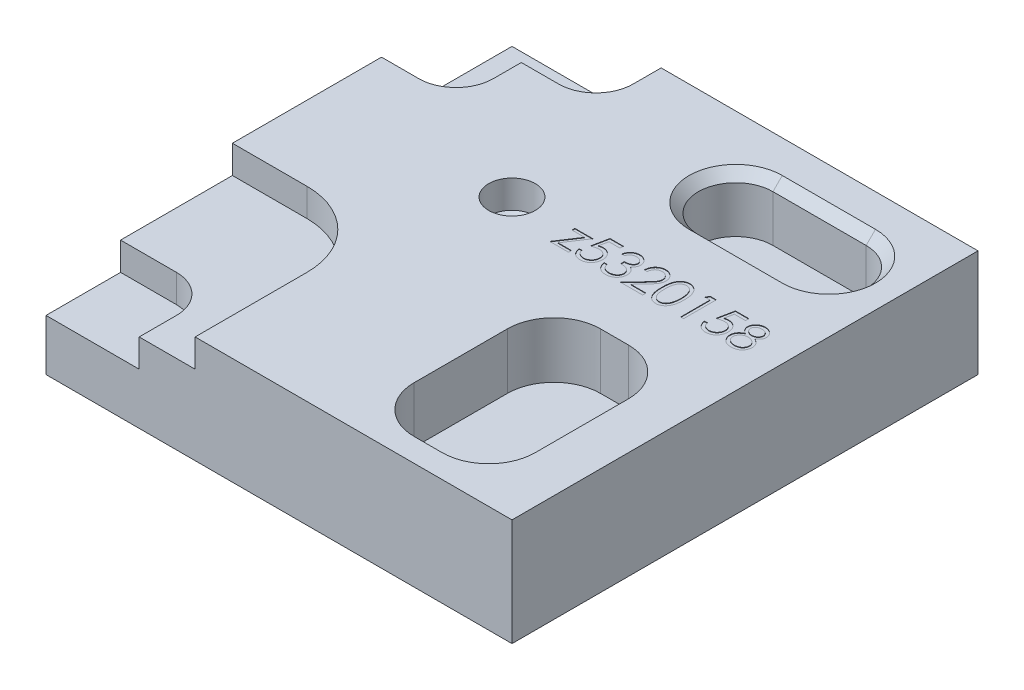
SolidWorks part; units mm, degrees
material "Alumina"
ref_plane "Front Plane" through (0, 0, 0) normal (0, 0, 1) x (1, 0, 0)
ref_plane "Top Plane" through (0, 0, 0) normal (0, 1, 0) x (1, 0, 0)
ref_plane "Right Plane" through (0, 0, 0) normal (1, 0, 0) x (0, 0, -1)
sketch "Sketch1" plane through (0, 0, 0) normal (0, 1, 0) x (1, 0, 0)
  line L0 (-4.643, 19.7567) -> (-4.643, 16.7567)
  line L1 (-20.643, 19.7567) -> (29.357, 19.7567)
  line L2 (-20.643, 19.7567) -> (-20.643, -30.2433)
  line L3 (-20.643, -30.2433) -> (29.357, -30.2433)
  line L4 (29.357, 19.7567) -> (29.357, -30.2433)
  line L5 (-20.643, 5.7567) -> (-16.643, 5.7567)
  line L6 (-12.643, 12.7567) -> (-12.643, 9.7567)
  line L7 (-12.643, 9.7567) -> (-12.643, 12.7567)
  line L8 (-8.643, 12.7567) -> (-12.643, 12.7567)
  line L9 (11.857, 7.2567) -> (21.857, 7.2567)
  line L15 (11.857, 15.2567) -> (21.857, 15.2567)
  line L17 (-20.643, -10.2433) -> (-12.643, -10.2433)
  line L18 (16.357, -5.2433) -> (19.357, -5.2433)
  line L19 (11.357, -10.2433) -> (11.357, -22.7433)
  line L20 (16.357, -27.7433) -> (19.357, -27.7433)
  line L21 (24.357, -10.2433) -> (24.357, -22.7433)
  line L22 (-4.643, -18.2433) -> (-4.643, -30.2433)
  line L23 (-20.643, -22.2433) -> (-14.643, -22.2433)
  line L24 (-10.643, -26.2433) -> (-10.643, -30.2433)
  arc A0 (-16.643, 5.7567) -> (-12.643, 9.7567) centre (-16.643, 9.7567) ccw
  arc A1 (-8.643, 12.7567) -> (-4.643, 16.7567) centre (-8.643, 16.7567) ccw
  arc A2 (21.857, 15.2567) -> (21.857, 7.2567) centre (21.857, 11.2567) cw
  arc A3 (11.857, 15.2567) -> (11.857, 7.2567) centre (11.857, 11.2567) ccw
  arc A4 (16.357, -5.2433) -> (11.357, -10.2433) centre (16.357, -10.2433) ccw
  arc A5 (24.357, -10.2433) -> (19.357, -5.2433) centre (19.357, -10.2433) ccw
  arc A6 (19.357, -27.7433) -> (24.357, -22.7433) centre (19.357, -22.7433) ccw
  arc A7 (11.357, -22.7433) -> (16.357, -27.7433) centre (16.357, -22.7433) ccw
  arc A8 (-10.643, -26.2433) -> (-14.643, -22.2433) centre (-14.643, -26.2433) ccw
  arc A9 (-4.643, -18.2433) -> (-12.643, -10.2433) centre (-12.643, -18.2433) ccw
  circle A10 centre (-0.643, -0.2433) radius 1.5
  circle A11 centre (-0.643, -0.2433) radius 2.5
  point P41 (-16.643, -10.2433)
  dimension "D7" = 4
  dimension "D8" = 4
  dimension "D11" = 4.5
  dimension "D13" = 5
  dimension "D14" = 5
  dimension "D15" = 5
  dimension "D16" = 5
  dimension "D21" = 4
  dimension "D22" = 8
  dimension "D27" = 3
  dimension "D28" = 5
  dimension "D1" = 50
  dimension "D2" = 50
  dimension "D3" = 14
  dimension "D4" = 16
  dimension "D5" = 8
  dimension "D6" = 7
  dimension "D9" = 10
  dimension "D10" = 8
  dimension "D12" = 7.5
  dimension "D17" = 22.5
  dimension "D18" = 18
  dimension "D19" = 5
  dimension "D20" = 2.5
  dimension "D23" = 10
  dimension "D24" = 20
  dimension "D25" = 8
  dimension "D26" = 16
  dimension "D29" = 30
  dimension "D30" = 20
extrude "Boss-Extrude1" add sketch "Sketch1" along normal blind 11.5 contours L3 L4 L1 L2
sketch "Sketch3" plane through (0, 11.5, 0) normal (0, 1, 0) x (1, 0, 0)
  line L0 (-20.643, -10.2433) -> (-12.643, -10.2433)
  line L1 (-20.643, 19.7567) -> (-20.643, -30.2433) construction
  line L2 (-4.643, -18.2433) -> (-4.643, -30.2433)
  line L3 (-20.643, -30.2433) -> (29.357, -30.2433) construction
  line L8 (-20.643, 19.7567) -> (-20.643, -30.2433)
  line L9 (-20.643, -30.2433) -> (29.357, -30.2433)
  line L10 (29.357, -30.2433) -> (29.357, 19.7567)
  line L11 (29.357, 19.7567) -> (-20.643, 19.7567)
  line L12 (-20.643, -10.2433) -> (-20.643, -30.2433)
  line L13 (-20.643, -30.2433) -> (-4.643, -30.2433)
  arc A0 (-4.643, -18.2433) -> (-12.643, -10.2433) centre (-12.643, -18.2433) ccw
  dimension "D1" = 8
  dimension "D2" = 20
  dimension "D3" = 16
  dimension "D4" = 0
extrude "Cut-Extrude1" cut sketch "Sketch3" against normal blind 3 contours L0 A0 L2 L13 L12
sketch "Sketch7" plane through (0, 8.5, 0) normal (0, 1, 0) x (1, 0, 0)
  line L0 (-20.643, -22.2433) -> (-14.643, -22.2433)
  line L1 (-20.643, -10.2433) -> (-20.643, -30.2433) construction
  line L2 (-10.643, -26.2433) -> (-10.643, -30.2433)
  line L3 (-20.643, -30.2433) -> (-4.643, -30.2433) construction
  arc A0 (-10.643, -26.2433) -> (-14.643, -22.2433) centre (-14.643, -26.2433) ccw
  dimension "D1" = 4
  dimension "D2" = 8
  dimension "D3" = 10
extrude "Cut-Extrude4" cut sketch "Sketch7" against normal blind 3 and the other way through all flip side to cut
sketch "Sketch8" plane through (0, 11.5, 0) normal (0, 1, 0) x (1, 0, 0)
  line L0 (-4.643, -30.2433) -> (29.357, -30.2433) construction
  line L1 (16.357, -7.7433) -> (19.357, -7.7433)
  line L2 (11.357, -12.7433) -> (11.357, -22.7433)
  line L3 (16.357, -27.7433) -> (19.357, -27.7433)
  line L4 (24.357, -12.7433) -> (24.357, -22.7433)
  line L5 (29.357, 19.7567) -> (29.357, -30.2433) construction
  arc A0 (16.357, -27.7433) -> (11.357, -22.7433) centre (16.357, -22.7433) cw
  arc A1 (19.357, -27.7433) -> (24.357, -22.7433) centre (19.357, -22.7433) ccw
  arc A2 (24.357, -12.7433) -> (19.357, -7.7433) centre (19.357, -12.7433) ccw
  arc A3 (16.357, -7.7433) -> (11.357, -12.7433) centre (16.357, -12.7433) ccw
  dimension "D1" = 5
  dimension "D2" = 22.5
  dimension "D3" = 2.5
  dimension "D4" = 5
  dimension "D5" = 18
extrude "Cut-Extrude5" cut sketch "Sketch8" against normal blind 6
sketch "Sketch9" plane through (0, 11.5, 0) normal (0, 1, 0) x (1, 0, 0)
  line L0 (-4.643, -30.2433) -> (29.357, -30.2433) construction
  line L1 (-20.643, 19.7567) -> (-20.643, -10.2433) construction
  circle A0 centre (-0.643, -0.2433) radius 1.5
  dimension "D1" = 3
  dimension "D2" = 30
  dimension "D3" = 20
sketch "Sketch11" plane through (0, 11.5, 0) normal (0, 1, 0) x (1, 0, 0)
  line L0 (29.357, 19.7567) -> (29.357, -30.2433) construction
  line L1 (11.857, 15.2567) -> (21.857, 15.2567)
  line L3 (11.857, 7.2567) -> (21.857, 7.2567)
  line L7 (-20.643, 19.7567) -> (29.357, 19.7567) construction
  arc A0 (21.857, 15.2567) -> (21.857, 7.2567) centre (21.857, 11.2567) cw
  arc A1 (11.857, 15.2567) -> (11.857, 7.2567) centre (11.857, 11.2567) ccw
  dimension "D1" = 10
  dimension "D3" = 8
  dimension "D2" = 7.5
  dimension "D4" = 4.5
extrude "Cut-Extrude8" cut sketch "Sketch11" against normal blind 6
sketch "Sketch12" plane through (0, 11.5, 0) normal (0, 1, 0) x (1, 0, 0)
  line L0 (-20.643, 5.7567) -> (-16.643, 5.7567)
  line L1 (-20.643, 19.7567) -> (-20.643, -10.2433) construction
  line L2 (-4.643, 19.7567) -> (-4.643, 16.7567)
  line L4 (-8.643, 12.7567) -> (-12.643, 12.7567)
  line L5 (-12.643, 12.7567) -> (-12.643, 9.7567)
  line L6 (-20.643, 19.7567) -> (29.357, 19.7567) construction
  arc A0 (-12.643, 9.7567) -> (-16.643, 5.7567) centre (-16.643, 9.7567) cw
  arc A1 (-8.643, 12.7567) -> (-4.643, 16.7567) centre (-8.643, 16.7567) ccw
  point P16 (-12.643, 11.2567)
  dimension "D1" = 4
  dimension "D2" = 4
  dimension "D3" = 14
  dimension "D4" = 16
  dimension "D5" = 8
  dimension "D6" = 7
extrude "Cut-Extrude11" cut sketch "Sketch12" against normal blind 6 and the other way through all flip side to cut contours L2 A1 L4 L5 A0 L0
chamfer "Chamfer1" distance 1 angle 45 4 edges at (7.857, 11.5, -11.2567) (16.857, 11.5, -7.2567) (25.857, 11.5, -11.2567) (16.857, 11.5, -15.2567)
hole_wizard "Ø3.0mm Dowel Hole1" positions "3DSketch3" profile "Sketch15" hole size "Ø3.0" standard "ANSI Metric"
sketch3d "3DSketch3"
  point P0 (-0.643, 11.5, 0.2433)
sketch "Sketch15" plane through (-0.643, 11.5, 0.2433) normal (1, 0, 0) x (0, 0, 1)
  line L0 (0, 0) -> (0, 6.9013)
  line L1 (0, 6.9013) -> (1.5, 6)
  line L2 (1.5, 6) -> (1.5, 0.025)
  line L3 (1.5, 0.025) -> (1.525, 0)
  line L5 (1.525, 0) -> (0, 0)
  line L6 (-1.5, 0.025) -> (-1.525, 0) construction
  line L10 (0, 6.9013) -> (-1.5, 6) construction
  line L11 (0, -6.35) -> (0, 107.95) construction
  dimension "Hole Dia." = 3
  dimension "Hole Depth" = 6
  dimension "Near C'Sink Dia." = 3.05
  dimension "Near C'Sink Angle" = 90
  dimension "Drill Angle" = 118
hole_wizard "Ø5.0mm Dowel Hole1" positions "3DSketch4" profile "Sketch16" hole size "Ø5.0" standard "ANSI Metric"
sketch3d "3DSketch4"
  point P0 (-0.643, 11.5, 0.2433)
sketch "Sketch16" plane through (-0.643, 11.5, 0.2433) normal (1, 0, 0) x (0, 0, 1)
  line L0 (0, 0) -> (0, 4.5022)
  line L1 (0, 4.5022) -> (2.5, 3)
  line L2 (2.5, 3) -> (2.5, 0)
  line L5 (2.5, 0) -> (0, 0)
  line L10 (0, 4.5022) -> (-2.5, 3) construction
  line L11 (0, -6.35) -> (0, 107.95) construction
  dimension "Hole Dia." = 5
  dimension "Hole Depth" = 3
  dimension "Drill Angle" = 118
sketch "Engrave" plane through (0, 11.5, 0) normal (0, 1, 0) x (1, 0, 0)
  text T0 "z5320158"
extrude "Engrave cut" cut sketch "Engrave" against normal blind 0.05
